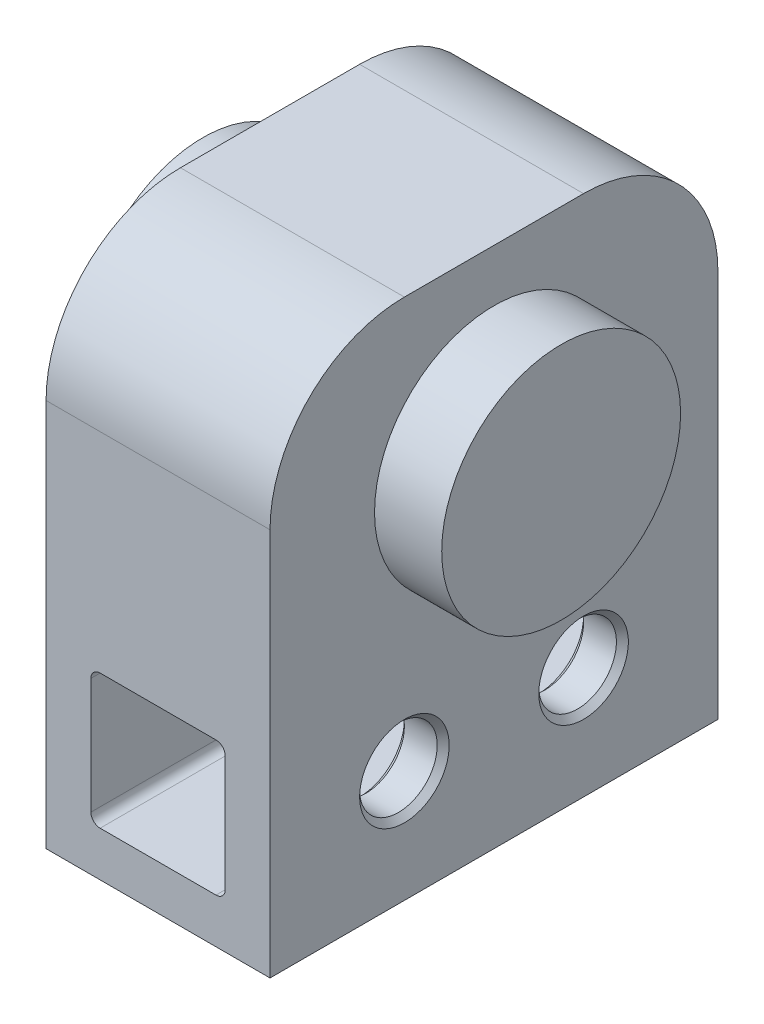
SolidWorks part; units mm, degrees
material "7075-O (SS)"
ref_plane "Front Plane" through (0, 0, 0) normal (0, 0, 1) x (1, 0, 0)
ref_plane "Top Plane" through (0, 0, 0) normal (0, 1, 0) x (1, 0, 0)
ref_plane "Right Plane" through (0, 0, 0) normal (1, 0, 0) x (0, 0, -1)
sketch "Sketch1" plane through (0, 0, 0) normal (0, 0, 1) x (1, 0, 0)
  line L1 (-37.5, -37.5) -> (37.5, -37.5)
  line L2 (-37.5, -37.5) -> (-37.5, 37.5)
  line L3 (-37.5, 37.5) -> (37.5, 37.5)
  line L4 (37.5, -37.5) -> (37.5, 37.5)
  line L5 (-37.5, -37.5) -> (37.5, 37.5) construction
  line L6 (-37.5, 37.5) -> (37.5, -37.5) construction
  point P0 (0, 0)
  dimension "D1" = 75
  dimension "D2" = 75
extrude "Boss-Extrude1" add sketch "Sketch1" along normal blind 150
sketch "Sketch5" plane through (0, 0, 150) normal (0, 0, 1) x (1, 0, 0)
  line L1 (-22.5, -22.5) -> (22.5, -22.5)
  line L2 (-22.5, -22.5) -> (-22.5, 22.5)
  line L3 (-22.5, 22.5) -> (22.5, 22.5)
  line L4 (22.5, -22.5) -> (22.5, 22.5)
  line L5 (-22.5, -22.5) -> (22.5, 22.5) construction
  line L6 (-22.5, 22.5) -> (22.5, -22.5) construction
  point P0 (0, 0)
  dimension "D1" = 45
  dimension "D2" = 45
extrude "Cut-Extrude2" cut sketch "Sketch5" against normal through all
fillet "Fillet2" radius 3.1 4 edges at (22.5, -22.5, 75) (22.5, 22.5, 75) (-22.5, 22.5, 75) (-22.5, -22.5, 75)
sketch "Sketch2" plane through (37.5, 0, 0) normal (1, 0, 0) x (0, 0, -1)
  line L0 (-150, 37.5) -> (0, 37.5)
  line L1 (0, 37.5) -> (0, 137.5)
  line L2 (0, 137.5) -> (-150, 137.5)
  line L3 (-150, 137.5) -> (-150, 37.5)
  dimension "D1" = 100
extrude "Boss-Extrude2" add sketch "Sketch2" against normal up to surface (75 mm away) up to face at (-37.5, 0, 75)
sketch "Sketch3" plane through (0, 0, 0) normal (1, 0, 0) x (0, 0, -1)
  line L0 (-75, 137.5) -> (-75, 22.5) construction
  line L4 (0, 22.5) -> (-150, 22.5) construction
  line L5 (-150, 137.5) -> (0, 137.5) construction
  circle A0 centre (-75, 80) radius 40
  dimension "D1" = 80
extrude "Hinge pins" add sketch "Sketch3" along normal mid plane 120
sketch "Sketch4" plane through (0, 0, 0) normal (-1, 0, 0) x (0, 0, 1)
  line L0 (105, 22.5) -> (105, -22.5) construction
  line L1 (45, 22.5) -> (45, -22.5) construction
  line L3 (150, -37.5) -> (150, 137.5) construction
  line L5 (105, 0) -> (45, 0) construction
  circle A0 centre (105, 0) radius 13
  circle A1 centre (45, 0) radius 13
  point P2 (75, 0)
  dimension "D1" = 26
  dimension "D2" = 26
  dimension "D3" = 60
  dimension "D4" = 75
extrude "Pin Holes" cut sketch "Sketch4" against normal through all both and the other way through all
chamfer "Chamfer1" distance 2 angle 45 8 edges at (-37.5, 0, 92) (37.5, 0, 118) (22.5, 0, 92) (-22.5, 0, 118) (-37.5, 0, 32) (22.5, 0, 32) (-22.5, 0, 58) (37.5, 0, 58)
fillet "Fillet4" radius 45 2 edges at (0, 137.5, 0) (0, 137.5, 150)
